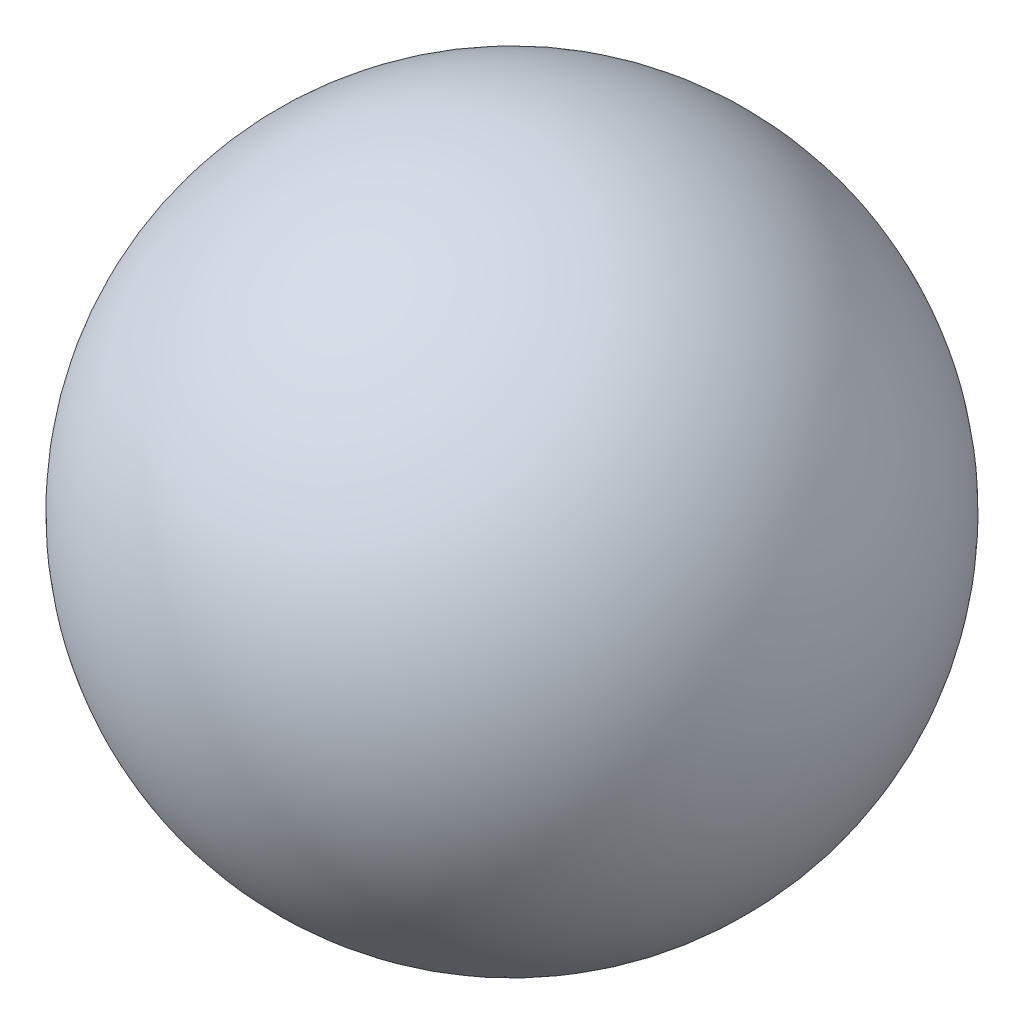
SolidWorks part; units mm, degrees
ref_plane "Front Plane" through (0, 0, 0) normal (0, 0, 1) x (1, 0, 0)
ref_plane "Top Plane" through (0, 0, 0) normal (0, 1, 0) x (1, 0, 0)
ref_plane "Right Plane" through (0, 0, 0) normal (1, 0, 0) x (0, 0, -1)
sketch "Sketch1" plane through (0, 0, 0) normal (0, 1, 0) x (1, 0, 0)
  line L0 (0, 44.45) -> (0, -44.45)
  arc A0 (0, 44.45) -> (0, -44.45) centre (0, 0) ccw
  arc A1 (0, 42.45) -> (0, -42.45) centre (0, 0) ccw
  dimension "D1" = 88.9
  dimension "D2" = 2
revolve "HollowBall" add sketch "Sketch1" angle 360 about L0 region at (-0.9939, 0, -43.45)
sketch3d "3DSketch1"
  line L0 (-58.7887, 35.3665, 0) -> (-82.864, 29.2077, 0)
  circle A0 centre (0, 0, 0) radius 44.45
  circle A1 centre (0, 0, 0) radius 27.4101
  circle A2 centre (0, 0, 0) radius 36.3342
  circle A3 centre (0, 0, 0) radius 40.5114
  circle A4 centre (0, 0, 0) radius 42.1336
  point P2 (0, 44.45, 0)
  point P5 (0, 27.4101, 0)
  point P7 (0, 36.3342, 0)
  point P9 (0, 40.5114, 0)
  point P11 (0, 42.1336, 0)
